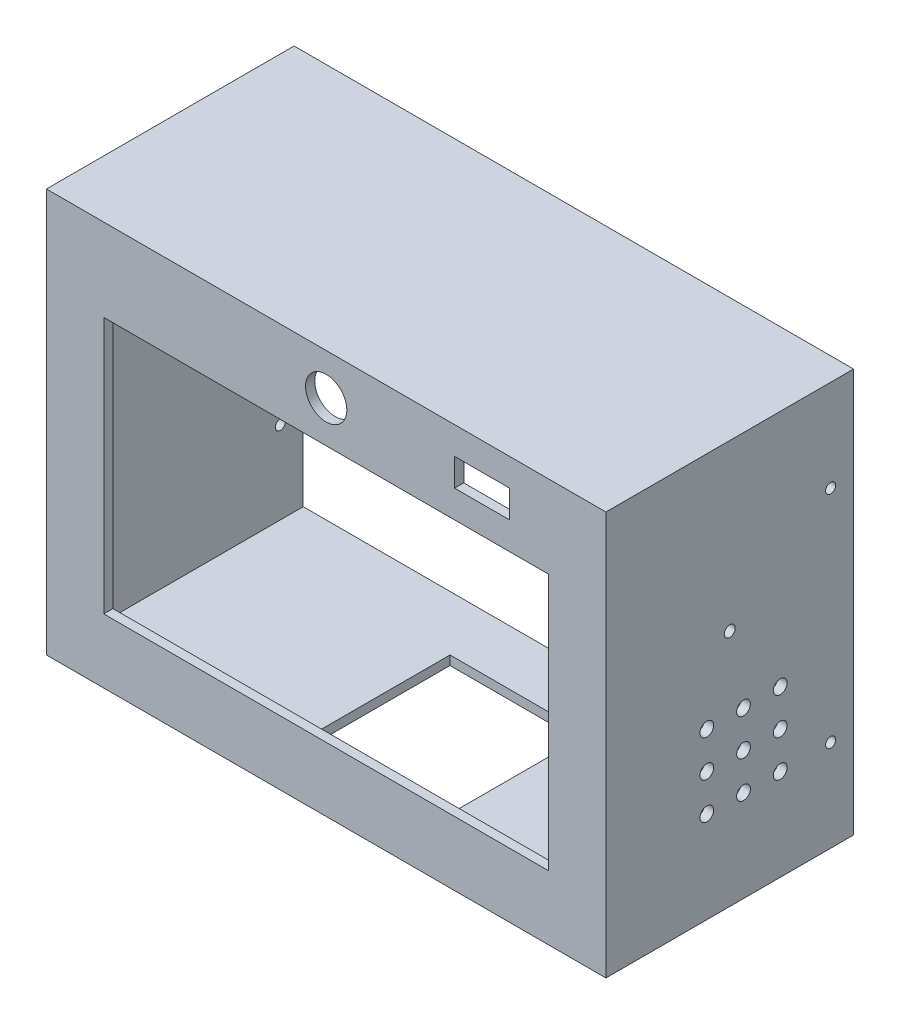
SolidWorks part; units mm, degrees
ref_plane "Front Plane" through (0, 0, 0) normal (0, 0, 1) x (1, 0, 0)
ref_plane "Top Plane" through (0, 0, 0) normal (0, 1, 0) x (1, 0, 0)
ref_plane "Right Plane" through (0, 0, 0) normal (1, 0, 0) x (0, 0, -1)
sketch "Sketch1" plane through (0, 0, 0) normal (0, 0, 1) x (1, 0, 0)
  line L1 (-61, 0) -> (61, 0)
  line L2 (-61, 0) -> (-61, 88)
  line L3 (-61, 88) -> (61, 88)
  line L4 (61, 0) -> (61, 88)
extrude "Boss-Extrude1" add sketch "Sketch1" along normal blind 54
sketch "Sketch2" plane through (0, 0, 0) normal (0, 0, 1) x (1, 0, 0)
  line L1 (-59, 2) -> (59, 2)
  line L2 (-59, 2) -> (-59, 86)
  line L3 (-59, 86) -> (59, 86)
  line L4 (59, 2) -> (59, 86)
extrude "Boss-Extrude2" add sketch "Sketch2" along normal blind 53 from offset 1 separate body offset against normal yes
combine bodies "Combine1" operation type subtract main body 101 bodies to subtract 102
sketch "Sketch3" plane through (0, 0, 0) normal (0, 0, 1) x (1, 0, 0)
  line L1 (-48.5, 14) -> (48.5, 14)
  line L2 (-48.5, 14) -> (-48.5, 70)
  line L3 (-48.5, 70) -> (48.5, 70)
  line L4 (48.5, 14) -> (48.5, 70)
extrude "Boss-Extrude3" add sketch "Sketch3" along normal blind 10 from offset 50 separate body
combine bodies "Combine2" operation type subtract main body 103 bodies to subtract 104
sketch "Sketch4" plane through (0, 0, 0) normal (0, 0, 1) x (1, 0, 0)
  circle A0 centre (0, 79) radius 4.5
extrude "Boss-Extrude4" add sketch "Sketch4" along normal blind 10 from offset 50 separate body
combine bodies "Combine3" operation type subtract main body 105 bodies to subtract 106
sketch "Sketch5" plane through (0, 0, 0) normal (0, 0, 1) x (1, 0, 0)
  line L1 (28, 76) -> (40, 76)
  line L2 (28, 76) -> (28, 82)
  line L3 (28, 82) -> (40, 82)
  line L4 (40, 76) -> (40, 82)
extrude "Boss-Extrude5" add sketch "Sketch5" along normal blind 10 from offset 50 separate body
combine bodies "Combine4" operation type subtract main body 107 bodies to subtract 108
sketch "Sketch6" plane through (0, 0, 0) normal (1, 0, 0) x (0, 0, -1)
  circle A0 centre (-27, 52) radius 1.2
extrude "Boss-Extrude6" add sketch "Sketch6" along normal blind 130 from offset 65 separate body offset against normal yes
combine bodies "Combine5" operation type subtract main body 109 bodies to subtract 110
sketch "Sketch7" plane through (0, 0, 0) normal (1, 0, 0) x (0, 0, -1)
  circle A0 centre (-16, 20) radius 1.5
extrude "Boss-Extrude7" add sketch "Sketch7" along normal blind 10 from offset 55 separate body
combine bodies "Combine6" operation type subtract main body 111 bodies to subtract 112
sketch "Sketch8" plane through (0, 0, 0) normal (1, 0, 0) x (0, 0, -1)
  circle A0 centre (-24, 20) radius 1.5
extrude "Boss-Extrude8" add sketch "Sketch8" along normal blind 10 from offset 55 separate body
combine bodies "Combine7" operation type subtract main body 113 bodies to subtract 114
sketch "Sketch9" plane through (0, 0, 0) normal (1, 0, 0) x (0, 0, -1)
  circle A0 centre (-32, 20) radius 1.5
extrude "Boss-Extrude9" add sketch "Sketch9" along normal blind 10 from offset 55 separate body
combine bodies "Combine8" operation type subtract main body 115 bodies to subtract 116
sketch "Sketch10" plane through (0, 0, 0) normal (1, 0, 0) x (0, 0, -1)
  circle A0 centre (-16, 28) radius 1.5
extrude "Boss-Extrude10" add sketch "Sketch10" along normal blind 10 from offset 55 separate body
combine bodies "Combine9" operation type subtract main body 117 bodies to subtract 118
sketch "Sketch11" plane through (0, 0, 0) normal (1, 0, 0) x (0, 0, -1)
  circle A0 centre (-24, 28) radius 1.5
extrude "Boss-Extrude11" add sketch "Sketch11" along normal blind 10 from offset 55 separate body
combine bodies "Combine10" operation type subtract main body 119 bodies to subtract 120
sketch "Sketch12" plane through (0, 0, 0) normal (1, 0, 0) x (0, 0, -1)
  circle A0 centre (-32, 28) radius 1.5
extrude "Boss-Extrude12" add sketch "Sketch12" along normal blind 10 from offset 55 separate body
combine bodies "Combine11" operation type subtract main body 121 bodies to subtract 122
sketch "Sketch13" plane through (0, 0, 0) normal (1, 0, 0) x (0, 0, -1)
  circle A0 centre (-16, 36) radius 1.5
extrude "Boss-Extrude13" add sketch "Sketch13" along normal blind 10 from offset 55 separate body
combine bodies "Combine12" operation type subtract main body 123 bodies to subtract 124
sketch "Sketch14" plane through (0, 0, 0) normal (1, 0, 0) x (0, 0, -1)
  circle A0 centre (-24, 36) radius 1.5
extrude "Boss-Extrude14" add sketch "Sketch14" along normal blind 10 from offset 55 separate body
combine bodies "Combine13" operation type subtract main body 125 bodies to subtract 126
sketch "Sketch15" plane through (0, 0, 0) normal (1, 0, 0) x (0, 0, -1)
  circle A0 centre (-32, 36) radius 1.5
extrude "Boss-Extrude15" add sketch "Sketch15" along normal blind 10 from offset 55 separate body
combine bodies "Combine14" operation type subtract main body 127 bodies to subtract 128
sketch "Sketch16" plane through (0, 0, 0) normal (0, 0, 1) x (1, 0, 0)
  line L1 (-15, -1) -> (15, -1)
  line L2 (-15, -1) -> (-15, 3)
  line L3 (-15, 3) -> (15, 3)
  line L4 (15, -1) -> (15, 3)
extrude "Boss-Extrude16" add sketch "Sketch16" along normal blind 30 from offset 12 separate body
combine bodies "Combine15" operation type subtract main body 129 bodies to subtract 130
sketch "Sketch17" plane through (0, 0, 0) normal (1, 0, 0) x (0, 0, -1)
  circle A0 centre (-5, 20) radius 1.1
extrude "Boss-Extrude17" add sketch "Sketch17" along normal blind 130 from offset 65 separate body offset against normal yes
combine bodies "Combine16" operation type subtract main body 131 bodies to subtract 132
sketch "Sketch18" plane through (0, 0, 0) normal (1, 0, 0) x (0, 0, -1)
  circle A0 centre (-5, 68) radius 1.1
extrude "Boss-Extrude18" add sketch "Sketch18" along normal blind 130 from offset 65 separate body offset against normal yes
combine bodies "Combine17" operation type subtract main body 133 bodies to subtract 134
